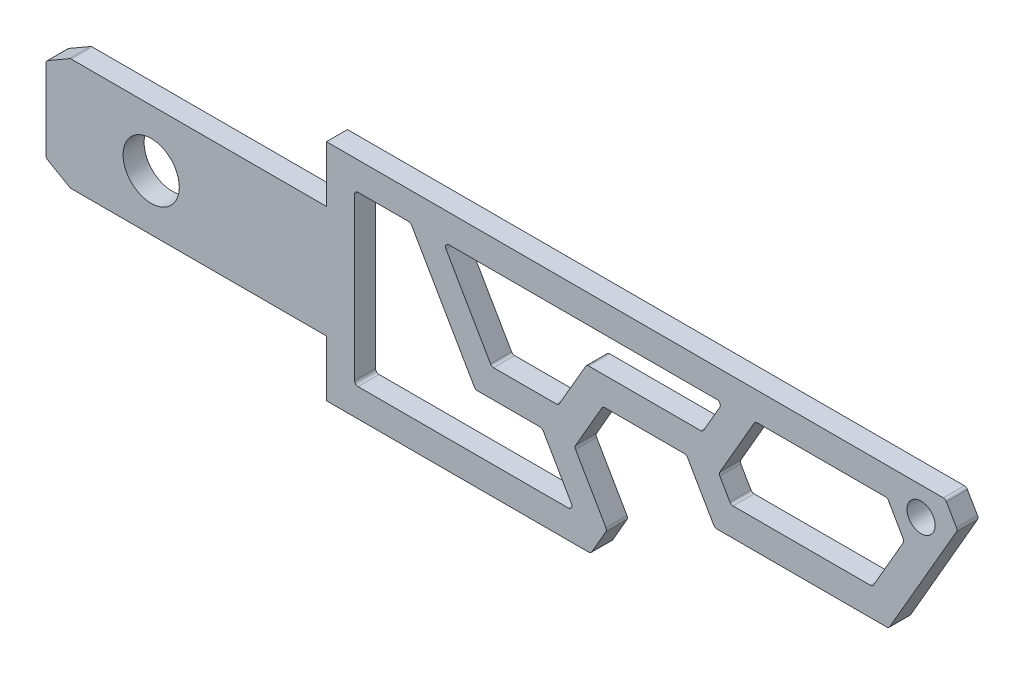
SolidWorks part; units mm, degrees
ref_plane "前视基准面" through (0, 0, 0) normal (0, 0, 1) x (1, 0, 0)
ref_plane "上视基准面" through (0, 0, 0) normal (0, 1, 0) x (1, 0, 0)
ref_plane "右视基准面" through (0, 0, 0) normal (1, 0, 0) x (0, 0, -1)
sketch "草图1" plane through (0, 0, 0) normal (0, 0, 1) x (1, 0, 0)
  line L0 (0, 81.9069) -> (0, 12) construction
  line L1 (0, 16) -> (88.2679, 16)
  line L2 (88.2679, 16) -> (90, 13)
  line L3 (0, -16) -> (37.6906, -16)
  line L4 (37.6906, -16) -> (40, -12)
  line L5 (40, -12) -> (96.5359, -12)
  line L6 (96.5359, -12) -> (100, -14)
  line L7 (0, 16) -> (0, 12)
  line L8 (-48.3677, 0) -> (26.6044, 0) construction
  line L9 (720, 54.3998) -> (724.5457, 58.1817)
  line L10 (724.5457, 58.1817) -> (770, 66)
  line L11 (770, 66) -> (770, 52)
  line L12 (90, 13) -> (0, 13) construction
  line L13 (720, 54.3998) -> (770, 63) construction
  line L14 (100, -14) -> (0, -14) construction
  line L15 (100, -14) -> (0, -16) construction
  line L16 (0, 12) -> (-40, 12)
  line L17 (0, -12) -> (-49.2119, -12)
  line L21 (0, -12) -> (0, -16)
  line L22 (0, 12) -> (0, 0) construction
  line L23 (0, -12) -> (0, -75.7106) construction
  line L24 (-99.0281, 9.7297) -> (-160.8449, 4.9675)
  line L27 (90, 13) -> (80.185, -4)
  line L28 (80.185, -4) -> (55.3812, -4)
  line L29 (55.3812, -4) -> (51.3397, 3)
  line L30 (51.3397, 3) -> (39.4226, 3)
  line L31 (39.4226, 3) -> (35.3812, -4)
  line L32 (35.3812, -4) -> (40, -12)
  line L33 (-140, -15.4919) -> (-159.1551, -16.9675)
  line L34 (-160.8449, 4.9675) -> (-160.6913, 2.9734) construction
  line L35 (0, 12) -> (0, -12)
  line L36 (4, 12) -> (4, -12)
  line L37 (4, -12) -> (35.3812, -12)
  line L38 (35.3812, -12) -> (30.7624, -4)
  line L39 (12, 12) -> (4, 12)
  line L41 (0, 8) -> (-36.5359, 8)
  line L42 (-40, 6) -> (-40, -6)
  line L43 (-36.5359, 8) -> (-40, 6)
  line L44 (16.6188, 12) -> (56.5359, 12)
  line L45 (16.6188, 12) -> (23.547, 0)
  line L46 (30.7624, -4) -> (21.2376, -4)
  line L47 (21.2376, -4) -> (12, 12)
  line L48 (23.547, 0) -> (33.0718, 0)
  line L49 (33.0718, 0) -> (37.1132, 7)
  line L50 (37.1132, 7) -> (53.6491, 7)
  line L51 (53.6491, 7) -> (56.5359, 12)
  line L52 (55.9585, 3) -> (57.6906, 0)
  line L53 (57.6906, 0) -> (77.8756, 0)
  line L54 (77.8756, 0) -> (82.4019, 7.8397)
  line L55 (80, 12) -> (61.1547, 12)
  line L56 (61.1547, 12) -> (55.9585, 3)
  line L57 (-160, -6) -> (-190, -8.3111) construction
  line L58 (-160.8449, 4.9675) -> (-161.3058, 10.9498)
  line L59 (-190, -8.3111) -> (-187.5332, 14.9471)
  line L60 (-187.5332, 14.9471) -> (-161.3058, 10.9498)
  line L61 (-184, -30.917) -> (-158.6942, -22.9498)
  line L62 (-190, -8.3111) -> (-184, -30.917)
  line L63 (-159.1551, -16.9675) -> (-158.6942, -22.9498)
  line L64 (-161.8426, 2.8847) -> (-167.3849, 2.4578)
  line L65 (-168.6898, 4.3632) -> (-167.3849, 2.4578)
  line L66 (-168.6898, 4.3632) -> (-179.6936, 3.5155)
  line L67 (-180.6913, 1.4327) -> (-179.3087, -16.5142)
  line L68 (-160.46, -15.0621) -> (-166.0023, -15.4891)
  line L69 (-167, -17.5719) -> (-166.0023, -15.4891)
  line L70 (-167, -17.5719) -> (-178.0038, -18.4196)
  line L71 (-36.5359, -8) -> (-40, -6)
  line L72 (0, -8) -> (-36.5359, -8)
  line L73 (-160.4622, 0) -> (-160, -6) construction
  line L74 (-159.3087, -14.9734) -> (-159.1551, -16.9675) construction
  line L75 (-160.6913, 2.9734) -> (-160.4622, 0) construction
  line L76 (-160, -6) -> (-159.3087, -14.9734) construction
  line L77 (-160.8449, 4.9675) -> (-161.8426, 2.8847)
  line L78 (-160.6913, 2.9734) -> (-161.8426, 2.8847) construction
  line L79 (-159.1551, -16.9675) -> (-160.46, -15.0621)
  line L80 (-159.3087, -14.9734) -> (-160.46, -15.0621) construction
  line L81 (-180.6913, 1.4327) -> (-179.6936, 3.5155)
  line L82 (-179.3087, -16.5142) -> (-178.0038, -18.4196)
  line L83 (30.7624, -4) -> (35.3812, -4)
  line L84 (80, 12) -> (82.4019, 7.8397)
  arc A0 (90, 13) -> (300, 14.8376) centre (90, 12013) ccw
  arc A1 (100, -14) -> (320, -7.1772) centre (-99.96, 9984.0006) ccw
  arc A2 (300, 14.8376) -> (720, 54.3998) centre (251.6491, 2777.3214) ccw
  arc A3 (320, -7.1772) -> (770, 52) centre (212.4689, 2551.0713) ccw
  arc A4 (-4, 0) -> (-160, -6) centre (-4, -2031) ccw construction
  circle A8 centre (-25, -0.1086) radius 4.01
  circle A9 centre (-120, -3.3154) radius 4.01
  arc A11 (-40, 12) -> (-99.0281, 9.7297) centre (-40, -756.5) ccw
  arc A13 (-49.2119, -12) -> (-140, -15.4919) centre (-49.2119, -1193.9919) ccw
  circle A14 centre (-170, -6.7704) radius 4.01
  circle A15 centre (84.8, 12) radius 2.01
  point P85 (-180, -7.5407)
  dimension "D1" = 770
  dimension "D3" = 300
  dimension "D16" = 52
  dimension "D17" = 50
  dimension "D19" = 12000
  dimension "D20" = 10000
  dimension "D22" = 4
  dimension "D24" = 160
  dimension "D29" = 40
  dimension "D30" = 8.02
  dimension "D32" = 8.02
  dimension "D23" = 11
  dimension "D33" = 20
  dimension "D27" = 8.02
  dimension "D69" = 4.02
  dimension "D2" = 32
  dimension "D4" = 450
  dimension "D5" = 60
  dimension "D6" = 60
  dimension "D7" = 30
  dimension "D8" = 30
  dimension "D9" = 14
  dimension "D10" = 100
  dimension "D11" = 90
  dimension "D12" = 3
  dimension "D13" = 4
  dimension "D14" = 2
  dimension "D15" = 40
  dimension "D18" = 11
  dimension "D21" = 2
  dimension "D25" = 6
  dimension "D26" = 30
  dimension "D28" = 24
  dimension "D31" = 40
  dimension "D34" = 25
  dimension "D35" = 46
  dimension "D36" = 60
  dimension "D37" = 20
  dimension "D38" = 12
  dimension "D39" = 13
  dimension "D40" = 20
  dimension "D41" = 4
  dimension "D42" = 4
  dimension "D43" = 4
  dimension "D44" = 60
  dimension "D45" = 4
  dimension "D46" = 40
  dimension "D47" = 30
  dimension "D48" = 12
  dimension "D49" = 4
  dimension "D50" = 4
  dimension "D51" = 4
  dimension "D52" = 4
  dimension "D53" = 4
  dimension "D54" = 4
  dimension "D55" = 4
  dimension "D56" = 4
  dimension "D57" = 8
  dimension "D58" = 16
  dimension "D59" = 20
  dimension "D60" = 18
  dimension "D61" = 34
  dimension "D62" = 6
  dimension "D63" = 60
  dimension "D64" = 60
  dimension "D65" = 10
  dimension "D66" = 7
  dimension "D67" = 60
  dimension "D68" = 10
  dimension "D70" = 5.2
extrude "凸台-拉伸1" add sketch "草图1" along normal mid plane 3 contours L7 L35 L21 L3 L4 L32 L31 L30 L29 L28 L27 L2 L1 | L72 L35 L41 L43 L42 L71 A8 region at (39.09, 3.2882, 0) region at (-19.3423, 0.0094, 0)
fillet "圆角1" radius 0.5 31 edges at (53.6491, 7, 0) (37.1132, 7, 0) (33.0718, 0, 0) (23.547, 0, 0) (57.6906, 0, 0) (61.1547, 12, 0) (55.9585, 3, 0) (77.8756, 0, 0) (82.4019, 7.8397, 0) (80, 12, 0) (88.2679, 16, 0) (37.6906, -16, 0) (80.185, -4, 0) (55.3812, -4, 0) (51.3397, 3, 0) (35.3812, -4, 0) (39.4226, 3, 0) (-36.5359, -8, 0) (-40, -6, 0) (-36.5359, 8, 0) (-40, 6, 0) (90, 13, 0) (40, -12, 0) (35.3812, -12, 0) (30.7624, -4, 0) (21.2376, -4, 0) (4, -12, 0) (12, 12, 0) (4, 12, 0) (56.5359, 12, 0) (16.6188, 12, 0)
